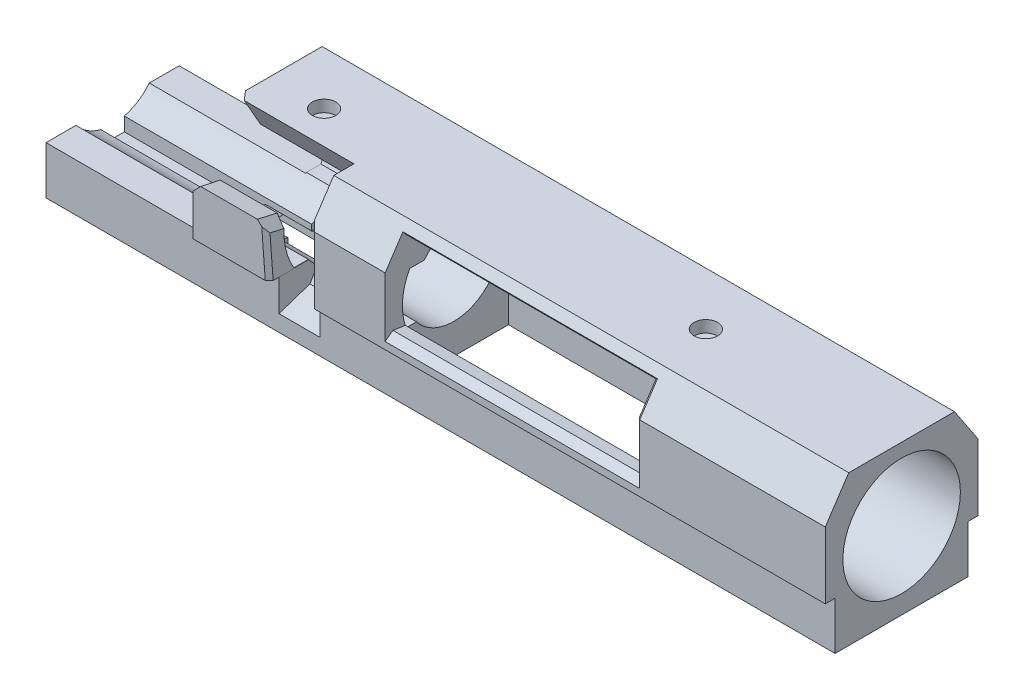
SolidWorks part; units mm, degrees
ref_plane "정면" through (0, 0, 0) normal (0, 0, 1) x (1, 0, 0)
ref_plane "윗면" through (0, 0, 0) normal (0, 1, 0) x (1, 0, 0)
ref_plane "우측면" through (0, 0, 0) normal (1, 0, 0) x (0, 0, -1)
sketch "스케치1" plane through (0, 0, 0) normal (0, 0, 1) x (1, 0, 0)
  line L0 (0, -26) -> (201.49, -26)
  line L1 (0, 0) -> (201.49, 0)
  line L2 (0, 0) -> (0, -38.22)
  line L3 (0, -38.22) -> (201.49, -38.22)
  line L4 (201.49, 0) -> (201.49, -38.22)
  dimension "D1" = 201.49
  dimension "D2" = 12.22
  dimension "D3" = 26
extrude "보스-돌출1" add sketch "스케치1" along normal mid plane 39 contours L4 L1 L2 L0 region at (100.745, -13, 0)
extrude "보스-돌출2" add sketch "스케치1<3>" along normal mid plane 34 contours L4 L0 L2 L3 region at (100.745, -32.11, 0)
sketch "스케치1<3>" plane through (0, 0, 0) normal (0, 0, 1) x (1, 0, 0) same geometry as "스케치1"
sketch "스케치2" plane through (0, 0, 0) normal (-1, 0, 0) x (0, 0, 1)
  line L3 (-3, -30.119) -> (-3, -33.619)
  line L4 (-3, -33.619) -> (3, -33.619)
  line L5 (3, -30.119) -> (3, -33.619)
  circle A0 centre (0, -18.5) radius 12
  point P6 (0, -30.5)
  point P8 (0, -33.619)
  dimension "D1" = 24
  dimension "D2" = 6
  dimension "D3" = 3.5
  dimension "D4" = 18.5
chamfer "모따기1" distance 6 distance2 9 1 edges at (100.745, 0, -19.5) first distance on face at (100.745, 0, 0)
chamfer "모따기2" distance 9 distance2 6 1 edges at (100.745, 0, 19.5) first distance on face at (100.745, -13, 19.5)
sketch "스케치4" plane through (0, 0, 0) normal (0, 0, 1) x (1, 0, 0)
  line L0 (0, -38.22) -> (34, -38.22)
  line L1 (0, -38.22) -> (201.49, -38.22) construction
  line L2 (34, -38.22) -> (53.1, -38.22)
  line L3 (34, -38.22) -> (38.6039, -33.6161)
  line L4 (38.6039, -33.6161) -> (47.8039, -33.6161)
  line L5 (47.8039, -33.6161) -> (53.1, -38.22)
  dimension "D1" = 34
  dimension "D2" = 19.1
  dimension "D3" = 9.2
  dimension "D4" = 135
  dimension "D5" = 41
extrude "컷-돌출2" cut sketch "스케치4" against normal mid plane 16 contours L2 L5 L4 L3
sketch "스케치5" plane through (0, 0, 0) normal (0, 0, 1) x (1, 0, 0)
  line L0 (0, -38.22) -> (33, -38.22)
  line L1 (0, -38.22) -> (201.49, -38.22) construction
  line L2 (33, -38.22) -> (33, -34.62)
  line L3 (36, -31.62) -> (58.2, -31.62)
  line L4 (58.2, -31.62) -> (58.2, -38.22)
  line L5 (58.2, -38.22) -> (33, -38.22)
  line L6 (36, -31.62) -> (33, -34.62)
  line L9 (58.2, -31.62) -> (47.8039, -31.62)
  line L10 (58.2, -31.62) -> (58.2, -28.12)
  line L11 (58.2, -28.12) -> (47.8039, -28.12)
  line L12 (47.8039, -31.62) -> (47.8039, -28.12)
  dimension "D1" = 33
  dimension "D2" = 25.2
  dimension "D3" = 6.6
  dimension "D4" = 3.5
  dimension "D5" = 45
  dimension "D6" = 3
extrude "컷-돌출3" cut sketch "스케치5" against normal mid plane 10.2 contours L2 L6 L3 L4 L5 | L10 L11 L12 L9
sketch "스케치8" plane through (0, 0, 0) normal (0, 0, 1) x (1, 0, 0)
  line L0 (0, 0) -> (201.49, 0) construction
  line L1 (0, -26) -> (40, -26)
  line L2 (0, -26) -> (0, 0)
  line L3 (0, 0) -> (40, 0)
  line L4 (40, -26) -> (40, 0)
  dimension "D1" = 40
extrude "컷-돌출4" cut sketch "스케치8" against normal through all both and the other way through all
extrude "컷-돌출13" cut sketch "스케치2" against normal blind 60 contours A0 L3 L4 L5 | A0 region at (0, -31.9944, 0)
extrude "컷-돌출14" cut sketch "스케치2<6>" against normal through all contours A0 | A0 region at (0, -18.5, 0)
sketch "스케치2<6>" plane through (0, 0, 0) normal (-1, 0, 0) x (0, 0, 1) same geometry as "스케치2"
sketch "스케치9" plane through (0, 0, 0) normal (0, 0, 1) x (1, 0, 0)
  line L0 (0, -38.22) -> (201.49, -38.22) construction
  line L1 (87.1, -22.72) -> (87.1, -38.22)
  line L2 (79.1, -22.72) -> (79.1, -38.22)
  line L4 (79.1, -38.22) -> (154.1, -38.22)
  line L5 (154.1, -38.22) -> (154.1, -22.72)
  line L6 (154.1, -22.72) -> (79.1, -22.72)
  dimension "D1" = 79.1
  dimension "D2" = 75
  dimension "D3" = 15.5
  dimension "D4" = 8
extrude "컷-돌출15" cut sketch "스케치9" against normal mid plane 28 contours L5 L6 L1 L4 region at (120.6, -30.47, 0)
sketch "스케치11" plane through (40, 0, 0) normal (-1, 0, 0) x (0, 0, 1)
  line L0 (13.5, 0) -> (17, -24)
ref_plane "평면1" through (0, 1.9278, 13.2189) normal (0, 0.1443, 0.9895) x (0, -0.9895, 0.1443)
sketch "스케치12" plane through (0, 1.9278, 13.2189) normal (0, 0.1443, 0.9895) x (0, -0.9895, 0.1443)
  line L0 (25, 79.1) -> (5, 79.1)
  line L1 (0, 0) -> (0, 79.1)
  line L2 (5, 89.1) -> (25, 89.1)
  line L3 (5, 79.1) -> (5, 153.1)
  line L4 (5, 153.1) -> (25, 153.1)
  line L5 (25, 153.1) -> (25, 79.1)
  dimension "D1" = 20
  dimension "D2" = 5
  dimension "D3" = 79.1
  dimension "D4" = 74
  dimension "D5" = 10
sketch "스케치14" plane through (0, 0, 0) normal (0, 0, 1) x (1, 0, 0)
extrude "컷-돌출16" cut sketch "스케치12" against normal mid plane 20 contours L5 L4 L3 L2 region at (121.1, -12.9152, 15.3835)
chamfer "모따기3" distance 2 angle 45 1 edges at (121.1, -22.4207, 19.5) first distance on face at (121.1, -22.8217, 16.75)
chamfer "모따기4" distance 1 angle 45 3 edges at (153.1, -5.9054, 17.437) (153.1, -16.5923, 19.5) (121.1, -2.8109, 15.3739) first distance on face at (153.1, -15.3127, 13.6414) first distance on face at (121.1, -3.6369, 9.7095)
sketch "스케치15" plane through (40, 0, 0) normal (-1, 0, 0) x (0, 0, 1)
  line L0 (-20.8732, -18.5) -> (19.999, -18.5) construction
  line L1 (9.5027, -11.1721) -> (13.2027, -11.1721)
  line L2 (9.5027, -25.8279) -> (13.2027, -25.8279)
  line L3 (0, 0) -> (0, -42.0989) construction
  line L4 (-9.5027, -25.8279) -> (-13.2027, -25.8279)
  line L5 (-9.5027, -11.1721) -> (-13.2027, -11.1721)
  arc A0 (-9.5027, -11.1721) -> (-9.5027, -25.8279) centre (0, -18.5) ccw
  arc A1 (13.2027, -25.8279) -> (13.2027, -11.1721) centre (0, -18.5) ccw
  arc A2 (9.5027, -25.8279) -> (9.5027, -11.1721) centre (0, -18.5) ccw
  arc A3 (-13.2027, -11.1721) -> (-13.2027, -25.8279) centre (0, -18.5) ccw
  point P4 (12, -18.5)
  point P5 (-12, -18.5)
  point P17 (-15.1, -18.5)
  arc M2 (-9.3675, -26) -> (9.3675, -26) centre (0, -18.5) cw
  dimension "D1" = 24
  dimension "D2" = 30.2
  dimension "D3" = 3.7
  dimension "D4" = 3.7
extrude "컷-돌출17" cut sketch "스케치15" against normal blind 134 contours L2 A1 L1 M2 | L5 A3 L4 A0 region at (40, -18.5, 12.8113)
ref_plane "평면2" through (175, 0, 0) normal (-1, 0, 0) x (0, 0, 1)
sketch "스케치16" plane through (175, 0, 0) normal (-1, 0, 0) x (0, 0, 1)
  line L0 (9.5027, -11.1721) -> (13.2027, -11.1721)
  line L1 (0, -18.5) -> (24.4696, -18.5) construction
  line L2 (0, -18.5) -> (7.2434, -39.5963) construction
  line L4 (-3.2514, -30.0511) -> (-2.0123, -33.4653)
  line L5 (0, -18.5) -> (-25.952, -18.5) construction
  line L6 (0, -18.5) -> (-8.9321, 7.5145) construction
  line L7 (-9.5027, -25.8279) -> (-13.2027, -25.8279)
  line L8 (2.3175, -3.5789) -> (3.4995, -7.0216)
  circle A0 centre (0, -18.5) radius 15.1
  circle A1 centre (0, -18.5) radius 12
  circle A2 centre (0, -18.5) radius 12 construction
  dimension "D1" = 71.05
  dimension "D3" = 71.05
  dimension "D4" = 3.64
extrude "컷-돌출18" cut sketch "스케치16" along normal blind 10 contours A1 L4 A0 L0 | A1 L8 A0 L7 region at (175, -11.4619, 11.3527) region at (175, -11.51, -10.1103)
sketch "스케치25" plane through (0, -25.8279, 0) normal (0, 1, 0) x (1, 0, 0)
  line L0 (165, -13.2027) -> (162, -13.2027)
  line L1 (165, -13.2027) -> (154.1, -13.2027) construction
  line L2 (165, -13.2027) -> (165, 2.0123)
  line L3 (165, 2.0123) -> (162, -13.2027)
  dimension "D1" = 3
extrude "컷-돌출20" cut sketch "스케치25" against normal up to surface up to face at (123.3429, -22.6009, 12.2013)
ref_plane "평면5" through (165, -11.1721, -9.5027) normal (-1, 0, 0) x (0, 0, 1)
sketch "스케치28" plane through (0, -11.1721, 0) normal (0, -1, 0) x (1, 0, 0)
  line L0 (165, -13.2027) -> (162, -13.2027)
  line L1 (165, -13.2027) -> (40, -13.2027) construction
  line L2 (165, -13.2027) -> (165, 2.3175)
  line L3 (165, 24.244) -> (165, -43.2494) construction
  line L4 (165, 2.3175) -> (175, 2.3175) construction
  line L5 (165, 2.3175) -> (162, -13.2027)
  dimension "D1" = 3
extrude "컷-돌출21" cut sketch "스케치28" against normal up to surface up to face at (124.24, -17.3872, -11.2665)
sketch "스케치29" plane through (201.49, 0, 0) normal (1, 0, 0) x (0, 0, -1)
  circle A0 centre (0, -18.5) radius 15
  dimension "D1" = 30
extrude "컷-돌출23" cut sketch "스케치29" against normal up to vertex (26.49 mm away) up to point (175, -11.1721, 9.5027)
sketch "스케치33" plane through (0, 0, -19.5) normal (0, 0, -1) x (-1, 0, 0)
  line L0 (-40, -26) -> (-40, -9) construction
  line L1 (-80, -13.5) -> (-55, -13.5)
  line L2 (-80, -13.5) -> (-80, -21.5)
  line L3 (-80, -21.5) -> (-55, -21.5)
  line L4 (-55, -13.5) -> (-55, -21.5)
  line L5 (-40, -26) -> (-201.49, -26) construction
  dimension "D1" = 25
  dimension "D2" = 15
  dimension "D3" = 8
  dimension "D4" = 4.5
extrude "컷-돌출25" cut sketch "스케치33" against normal blind 4
sketch "스케치34" plane through (0, 0, -15.5) normal (0, 0, -1) x (-1, 0, 0)
  line L0 (-80, -17.5) -> (-55, -17.5) construction
  line L1 (-80, -13.5) -> (-80, -21.5) construction
  line L2 (-55, -21.5) -> (-55, -13.5) construction
  line L3 (-40, -26) -> (-40, -9) construction
  line L4 (-60, -20.1879) -> (-56, -20.1879)
  line L5 (-60, -20.1879) -> (-60, -14.8121)
  line L6 (-60, -14.8121) -> (-56, -14.8121)
  line L7 (-56, -20.1879) -> (-56, -14.8121)
  line L8 (-60, -20.1879) -> (-56, -14.8121) construction
  line L9 (-60, -14.8121) -> (-56, -20.1879) construction
  line L10 (-60, -20.1879) -> (-63, -20.1879)
  line L11 (-63, -20.1879) -> (-63, -14.8121)
  line L12 (-63, -14.8121) -> (-60, -14.8121)
  circle A0 centre (-76, -17.5) radius 1.3029
  point P8 (-58, -17.5)
  dimension "D1" = 18
  dimension "D2" = 3
  dimension "D3" = 4
  dimension "D4" = 4
extrude "컷-돌출26" cut sketch "스케치34" against normal up to surface (0.4946 mm away) contours L12 L11 L10 L5 | L4 L7 L6 L5 region at (58, -17.5, -15.5) region at (61.5, -17.5, -15.5) up to face at (123.9169, -17.3872, -11.2665)
sketch "스케치35" plane through (0, -13.5, 0) normal (0, -1, 0) x (1, 0, 0)
  line L0 (55, -19.5) -> (80, -19.5) construction
  line L1 (55, -15.5) -> (55, -19.5) construction
  circle A0 centre (67.5, -17.5) radius 1
  dimension "D1" = 2
  dimension "D2" = 2
  dimension "D3" = 12.5
extrude "보스-돌출3" add sketch "스케치34<4>" along normal blind 1.5 contours A0 region at (76, -17.5, -15.5)
sketch "스케치34<4>" plane through (0, 0, -15.5) normal (0, 0, -1) x (-1, 0, 0) same geometry as "스케치34"
extrude "컷-돌출28" cut sketch "스케치35" against normal mid plane 25
fillet "필렛1" radius 0.5 4 edges at (55, -17.5, -15.5) (67.5, -21.5, -15.5) (67.5, -13.5, -15.5) (80, -17.5, -15.5)
fillet "필렛2" radius 0.5 1 edges at (74.6971, -17.5, -17)
sketch "스케치37" plane through (40, 0, 0) normal (-1, 0, 0) x (0, 0, 1)
  line L0 (10.7225, 4.1662) -> (4.253, -7.279)
  line L1 (19.5, -9) -> (13.5, 0) construction
  line L2 (19.5, -13.4482) -> (14.557, -14.4872)
  line L3 (19.5, -26) -> (19.5, -9) construction
  line L4 (9.5027, -11.1721) -> (13.2027, -11.1721) construction
  line L5 (19.5, -9) -> (10.7225, 4.1662)
  line L6 (19.5, -13.4482) -> (19.5, -9)
  line L7 (9.5027, -11.1721) -> (13.2027, -11.1721)
  arc A0 (9.5027, -11.1721) -> (-9.5027, -11.1721) centre (0, -18.5) ccw construction
  arc A1 (13.2027, -25.8279) -> (13.2027, -11.1721) centre (0, -18.5) ccw construction
  arc A2 (14.557, -14.4872) -> (13.2027, -11.1721) centre (0, -18.5) ccw
  arc A3 (9.5027, -11.1721) -> (4.253, -7.279) centre (0, -18.5) ccw
extrude "컷-돌출29" cut sketch "스케치37" against normal blind 30
sketch "스케치38" plane through (70, 0, 0) normal (-1, 0, 0) x (0, 0, 1)
  line L0 (19.5, -13.4482) -> (19.5, -48.4392)
  line L1 (19.5, -26) -> (19.5, -13.4482) construction
  line L2 (19.5, -48.4392) -> (8.7376, -30.8152)
  line L3 (19.5, -13.4482) -> (19.5, -48.4392)
  line L4 (19.5, -13.4482) -> (14.557, -14.4872)
  line L5 (13.2027, -25.8279) -> (9.5027, -25.8279)
  line L6 (8.7376, -30.8152) -> (7.1171, -28.1616)
  arc A0 (13.2027, -25.8279) -> (14.557, -14.4872) centre (0, -18.5) ccw construction
  arc A2 (8.7376, -30.8152) -> (14.557, -14.4872) centre (0, -18.5) ccw
  arc A4 (7.1171, -28.1616) -> (9.5027, -25.8279) centre (0, -18.5) ccw
  line M5 (14.557, -14.4872) -> (19.5, -13.4482)
extrude "컷-돌출30" cut sketch "스케치38" along normal blind 10.5 contours A2 L2 L0 M5 | A4 L6 A2 L5 region at (70, -30.0293, 16.1321) region at (70, -27.8482, 9.9276)
sketch "스케치40" plane through (0, 0, 19.5) normal (0, 0, 1) x (1, 0, 0)
  line L0 (58.5, -13.4482) -> (59.5, -26)
  line L1 (59.5, -13.4482) -> (40, -13.4482) construction
  line L2 (59.5, -26) -> (59.5, -13.4482)
  line L3 (59.5, -13.4482) -> (58.5, -13.4482)
  dimension "D1" = 1
extrude "컷-돌출31" cut sketch "스케치40" against normal up to next
chamfer "모따기5" distance 2 angle 45 3 edges at (40, -13.9677, 17.0285) (40, -3.6395, 6.3103) (58.5414, -13.9677, 17.0285) first distance on face at (40, -22.5321, 14.8206) first distance on face at (40, -15.0916, -10.3817) first distance on face at (49.2707, -13.9677, 17.0285)
sketch "스케치41" plane through (70, 0, 0) normal (-1, 0, 0) x (0, 0, 1)
  line L0 (9.1165, -31.4357) -> (17, -34.0771)
  line L2 (17, -26) -> (17, -38.22) construction
  line L3 (17, -34.0771) -> (17, -38.22)
  line L4 (17, -38.22) -> (13.2595, -38.22)
  line L5 (13.2595, -38.22) -> (9.1165, -31.4357)
  line L6 (13.2595, -38.22) -> (7.1171, -28.1616) construction
extrude "보스-돌출4" add sketch "스케치41" along normal up to surface (10.5 mm away) up to face at (59.5, -31.335, 12.7629)
sketch "스케치42" plane through (0, 0, 0) normal (0, 1, 0) x (1, 0, 0)
  line L0 (40, 13.5) -> (40, -6.0701) construction
  line L1 (201.49, -13.5) -> (201.49, 13.5) construction
  circle A0 centre (151.49, 0) radius 3
  circle A1 centre (54, 0) radius 3
  point P6 (201.49, 0)
  dimension "D1" = 6
  dimension "D2" = 6
  dimension "D3" = 14
  dimension "D4" = 50
extrude "컷-돌출32" cut sketch "스케치42" against normal blind 3
chamfer "모따기7" distance 1 angle 45 2 edges at (70, -17.5, 19.5) (59.0883, -20.8324, 19.5)
